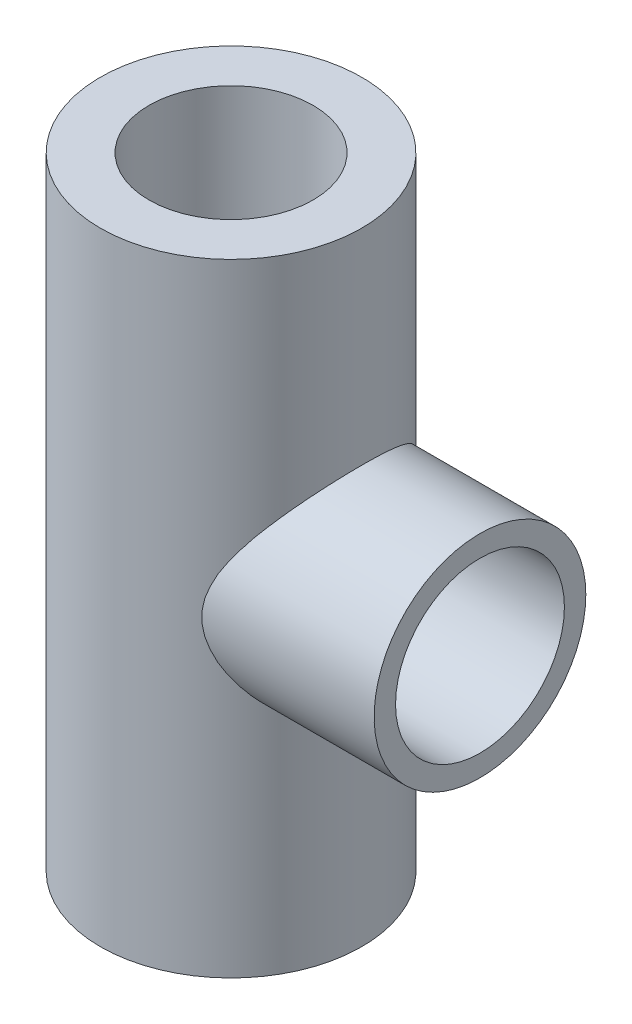
SolidWorks part; units mm, degrees
ref_plane "Front Plane" through (0, 0, 0) normal (0, 0, 1) x (1, 0, 0)
ref_plane "Top Plane" through (0, 0, 0) normal (0, 1, 0) x (1, 0, 0)
ref_plane "Right Plane" through (0, 0, 0) normal (1, 0, 0) x (0, 0, -1)
sketch "Sketch1" plane through (0, 0, 0) normal (0, 1, 0) x (1, 0, 0)
  circle A0 centre (0, 0) radius 16.6751
  circle A1 centre (0, 0) radius 10.4648
  dimension "D1" = 20.9296
  dimension "D2" = 33.3502
extrude "Boss-Extrude1" add sketch "Sketch1" along normal mid plane 79.375
sketch "Sketch2" plane through (0, 0, 0) normal (1, 0, 0) x (0, 0, -1)
  circle A0 centre (0, 0) radius 13.5001
  circle A1 centre (0, 0) radius 7.8994
  dimension "D1" = 27.0002
  dimension "D2" = 15.7988
ref_plane "Plane1" through (31.75, 0, 0) normal (1, 0, 0) x (0, 0, -1)
extrude "Boss-Extrude2" add sketch "Sketch2" along normal up to surface (31.75 mm away) separate body up to plane "Plane1"
sketch "Sketch4" plane through (31.75, 0, 0) normal (1, 0, 0) x (0, 0, -1)
  circle A0 centre (0, 0) radius 7.8994 construction
  circle A1 centre (0, 0) radius 7.8994
extrude "Cut-Extrude3" cut sketch "Sketch4" against normal up to surface (31.75 mm away) up to plane "Right Plane"
sketch "Sketch5" plane through (0, 39.6875, 0) normal (0, 1, 0) x (1, 0, 0)
  circle A0 centre (0, 0) radius 10.4648 construction
  circle A1 centre (0, 0) radius 10.4648
extrude "Cut-Extrude4" cut sketch "Sketch5" against normal up to surface (79.375 mm away) up to face at (0, -39.6875, 16.6751)
sketch "Sketch6" plane through (31.75, 0, 0) normal (1, 0, 0) x (0, 0, -1)
  circle A0 centre (0, 0) radius 13.5001 construction
  circle A1 centre (0, 0) radius 13.5001 construction
  circle A2 centre (0, 0) radius 10.7696
  dimension "D1" = 21.5392
extrude "Cut-Extrude5" cut sketch "Sketch6" against normal blind 17.526
